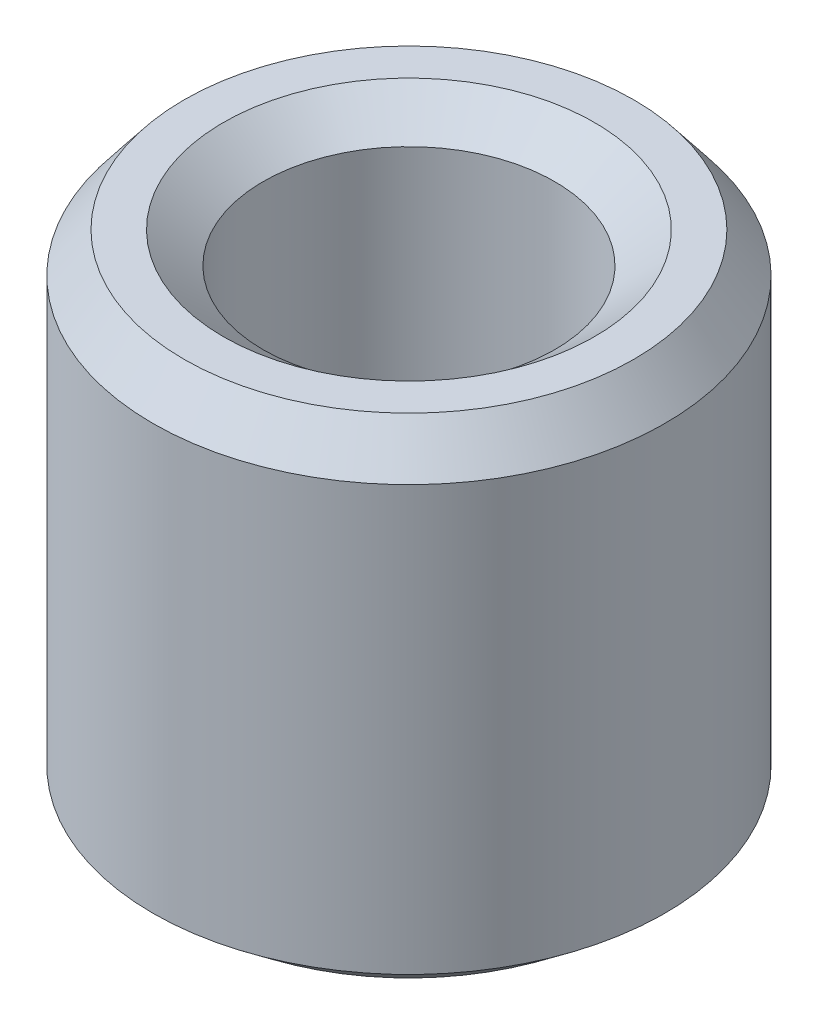
SolidWorks part; units mm, degrees
ref_plane "Front Plane" through (0, 0, 0) normal (0, 0, 1) x (1, 0, 0)
ref_plane "Top Plane" through (0, 0, 0) normal (0, 1, 0) x (1, 0, 0)
ref_plane "Right Plane" through (0, 0, 0) normal (1, 0, 0) x (0, 0, -1)
sketch "Sketch1" plane through (0, 0, 0) normal (0, 1, 0) x (1, 0, 0)
  circle A0 centre (0, 0) radius 10
  dimension "SLEEVE_OD" = 20
extrude "Boss-Extrude1" add sketch "Sketch1" along normal blind 19.3417
sketch "Sketch2" plane through (0, 0, 0) normal (0, 1, 0) x (1, 0, 0)
  circle A0 centre (0, 0) radius 5.6911
  dimension "BORE_D" = 11.3822
extrude "Cut-Extrude1" cut sketch "Sketch2" along normal through all
chamfer "Chamfer1" distance 1.5561 angle 38.086 4 edges at (0, 19.3417, 5.6911) (0, 0, 5.6911) (0, 0, 10) (0, 19.3417, 10) first distance on face at (0, 19.3417, 5.6911) first distance on face at (0, 0, 5.6911) first distance on face at (0, 19.3417, 10)
